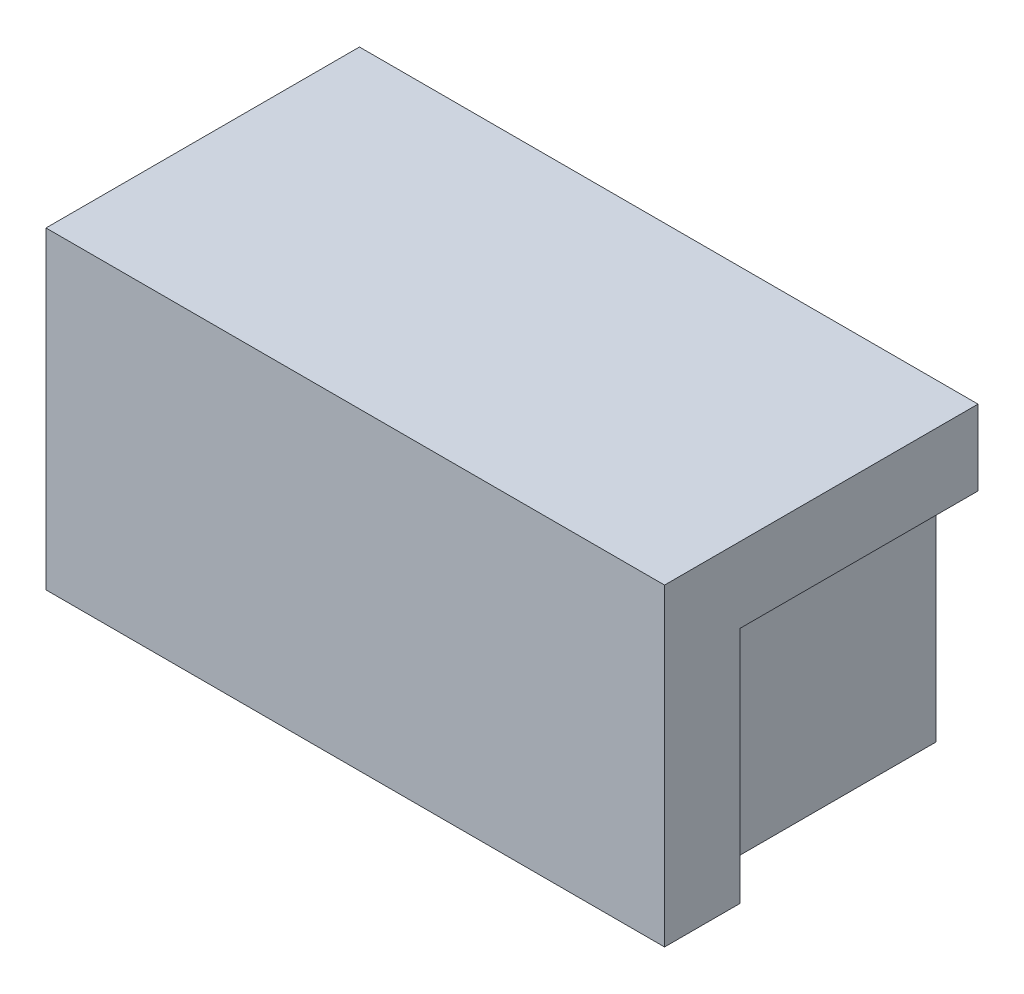
SolidWorks part; units mm, degrees
ref_plane "Front Plane" through (0, 0, 0) normal (0, 0, 1) x (1, 0, 0)
ref_plane "Top Plane" through (0, 0, 0) normal (0, 1, 0) x (1, 0, 0)
ref_plane "Right Plane" through (0, 0, 0) normal (1, 0, 0) x (0, 0, -1)
sketch "Sketch1" plane through (0, 0, 0) normal (1, 0, 0) x (0, 0, -1)
  line L0 (-7.5, -7.5) -> (7.5, -7.5)
  line L2 (-7.5, -7.5) -> (-7.5, 7.5)
  line L3 (-7.5, 7.5) -> (7.5, 7.5)
  line L4 (7.5, -7.5) -> (7.5, 7.5)
  line L5 (-7.5, -7.5) -> (7.5, 7.5) construction
  line L6 (-7.5, 7.5) -> (7.5, -7.5) construction
  line L7 (-7.5, 7.5) -> (7.5, 7.5)
  line L8 (-7.5, 7.5) -> (-7.5, 3.9)
  line L9 (-7.5, 3.9) -> (7.5, 3.9)
  line L10 (7.5, 7.5) -> (7.5, 3.9)
  line L11 (-7.5, 7.5) -> (-3.9, 7.5)
  line L12 (-7.5, 7.5) -> (-7.5, -7.5)
  line L13 (-7.5, -7.5) -> (-3.9, -7.5)
  line L14 (-3.9, 7.5) -> (-3.9, -7.5)
  line L15 (7.5, -7.5) -> (3.9, -7.5)
  line L16 (7.5, -7.5) -> (7.5, 7.5)
  line L17 (7.5, 7.5) -> (3.9, 7.5)
  line L18 (3.9, -7.5) -> (3.9, 7.5)
  circle A0 centre (0, 0) radius 1.8
  point P0 (0, 0)
  dimension "D2" = 3.6
  dimension "D1" = 15
  dimension "D3" = 3.6
extrude "Boss-Extrude1" add sketch "Sketch1" against normal blind 3.6 contours L18 L0 L4 L9 | L18 L9 L4 L3 | L9 L18 L7 L14 | L14 L3 L2 L9 | L14 L9 L2 L0 | L0 L18 L9 L14 A0 region at (0, -1.8, 5.7) region at (0, -2.0327, 0) region at (0, 5.7, 5.7) region at (0, -1.8, -5.7) region at (0, 5.7, 0) region at (0, 5.7, -5.7)
extrude "Boss-Extrude2" add sketch "Sketch1<3>" along normal blind 22 contours L14 L9 L2 L0 | L14 L3 L2 L9 | L9 L18 L7 L14 | L18 L9 L4 L3 | L18 L0 L4 L9 region at (0, -1.8, 5.7) region at (0, 5.7, 5.7) region at (0, -1.8, -5.7) region at (0, 5.7, 0) region at (0, 5.7, -5.7)
sketch "Sketch1<3>" plane through (0, 0, 0) normal (1, 0, 0) x (0, 0, -1) same geometry as "Sketch1"
sketch "Sketch2" plane through (22, 0, 0) normal (1, 0, 0) x (0, 0, -1)
  line L0 (-3.9, 3.9) -> (-3.9, -7.5) construction
  line L1 (-7.5, 7.5) -> (7.5, 7.5)
  line L2 (-7.5, 7.5) -> (-7.5, -7.5)
  line L3 (-7.5, -7.5) -> (7.5, -7.5)
  line L4 (7.5, 7.5) -> (7.5, -7.5)
  line L5 (-7.5, 7.5) -> (-3.9, 7.5)
  line L6 (-7.5, 7.5) -> (-7.5, -7.5)
  line L7 (-7.5, -7.5) -> (-3.9, -7.5)
  line L8 (-3.9, 7.5) -> (-3.9, -7.5)
  line L9 (-3.9, 3.9) -> (3.9, 3.9) construction
  line L10 (-7.5, 7.5) -> (7.5, 7.5)
  line L11 (-7.5, 7.5) -> (-7.5, 3.9)
  line L12 (-7.5, 3.9) -> (7.5, 3.9)
  line L13 (7.5, 7.5) -> (7.5, 3.9)
  line M2 (-3.9, -7.5) -> (-3.9, 3.9)
  line M3 (-3.9, 3.9) -> (3.9, 3.9)
  line M4 (3.9, 3.9) -> (3.9, -7.5)
  line M5 (3.9, -7.5) -> (7.5, -7.5)
  line M6 (7.5, -7.5) -> (7.5, 7.5)
  line M7 (7.5, 7.5) -> (-7.5, 7.5)
  line M8 (-7.5, 7.5) -> (-7.5, -7.5)
  line M9 (-7.5, -7.5) -> (-3.9, -7.5)
extrude "Boss-Extrude3" add sketch "Sketch2" along normal blind 2 contours L12 M4 M5 M6 | L3 M2 M4 M3 | L12 L4 L8 M3 M7 | L12 L8 L1 M8 | L12 L6 M9 M2 region at (22, 5.7, 5.7) region at (22, 5.7, -1.8) region at (22, -1.8, 5.7) region at (22, -1.8, 0) region at (22, -1.8, -5.7)
extrude "Boss-Extrude4" add sketch "Sketch2<3>" along normal blind 4 contours L12 L4 L8 M3 M7 | L12 L8 L1 M8 | L12 L6 M9 M2 region at (22, 5.7, 5.7) region at (22, 5.7, -1.8) region at (22, -1.8, 5.7)
sketch "Sketch2<3>" plane through (22, 0, 0) normal (1, 0, 0) x (0, 0, -1) same geometry as "Sketch2"
